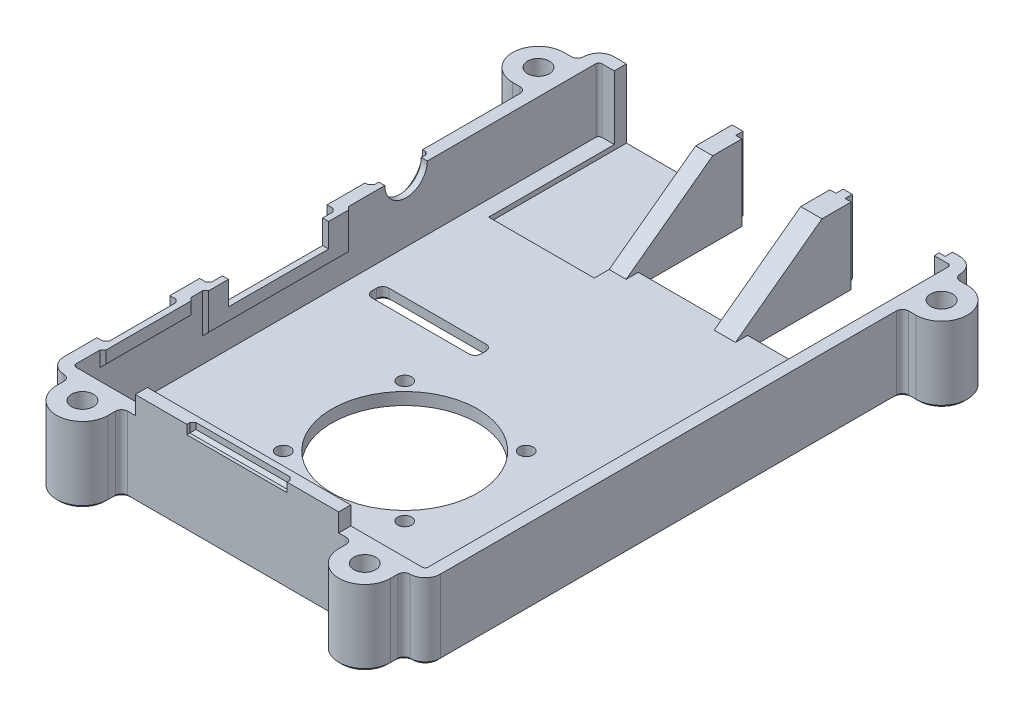
SolidWorks part; units mm, degrees
ref_plane "Front Plane" through (0, 0, 0) normal (0, 0, 1) x (1, 0, 0)
ref_plane "Top Plane" through (0, 0, 0) normal (0, 1, 0) x (1, 0, 0)
ref_plane "Right Plane" through (0, 0, 0) normal (1, 0, 0) x (0, 0, -1)
sketch "Sketch2" plane through (0, 0, 0) normal (0, 1, 0) x (1, 0, 0)
  line L1 (2.5, 0) -> (59.5, 0)
  line L2 (0, 2.5) -> (0, 88.1)
  line L3 (2.5, 90.6) -> (59.5, 90.6)
  line L4 (62, 2.5) -> (62, 88.1)
  arc A0 (0, 2.5) -> (2.5, 0) centre (2.5, 2.5) ccw
  arc A1 (59.5, 0) -> (62, 2.5) centre (59.5, 2.5) ccw
  arc A2 (62, 88.1) -> (59.5, 90.6) centre (59.5, 88.1) ccw
  arc A3 (2.5, 90.6) -> (0, 88.1) centre (2.5, 88.1) ccw
  point P7 (0, 0)
  point P10 (62, 0)
  point P13 (62, 90.6)
  point P16 (0, 90.6)
  dimension "D3" = 2.5
  dimension "D1" = 62
  dimension "D2" = 90.6
extrude "Base" add sketch "Sketch2" along normal blind 12.5
shell "Shell" thickness 2 removed face at (31, 12.5, -45.3)
sketch "Sketch14" plane through (0, 0, 0) normal (0, -1, 0) x (1, 0, 0)
  line L0 (31, 0) -> (31, -90.6) construction
  line L2 (59.5, -90.6) -> (2.5, -90.6) construction
  line L3 (-2.2, -78.6) -> (0, -78.6)
  line L4 (0, -88.1) -> (0, -2.5) construction
  line L5 (0, -78.6) -> (0, -87.1)
  line L6 (0, -87.1) -> (-2.2, -87.1)
  line L7 (3.5, 2.2) -> (3.5, 0)
  line L8 (2.5, 0) -> (59.5, 0) construction
  line L9 (3.5, 0) -> (12, 0)
  line L10 (12, 0) -> (12, 2.2)
  line L11 (64.2, -78.6) -> (62, -78.6)
  line L12 (62, -87.1) -> (64.2, -87.1)
  line L13 (62, -78.6) -> (62, -87.1)
  line L14 (50, 0) -> (50, 2.2)
  line L15 (58.5, 0) -> (50, 0)
  line L16 (58.5, 2.2) -> (58.5, 0)
  line L17 (2.5, 0) -> (59.5, 0) construction
  arc A0 (-2.2, -78.6) -> (-2.2, -87.1) centre (-2.2, -82.85) ccw
  arc A1 (3.5, 2.2) -> (12, 2.2) centre (7.75, 2.2) cw
  arc A2 (64.2, -78.6) -> (64.2, -87.1) centre (64.2, -82.85) cw
  arc A3 (58.5, 2.2) -> (50, 2.2) centre (54.25, 2.2) ccw
  dimension "D1" = 2.2
  dimension "D2" = 8.5
  dimension "D3" = 3.5
  dimension "D4" = 3.5
extrude "Clamps" add sketch "Sketch14" against normal up to surface (12.5 mm away) up to face at (31, 12.5, -45.3)
fillet "Clamp Fillets" radius 1 8 edges at (50, 6.25, 0) (58.5, 6.25, 0) (12, 6.25, 0) (3.5, 6.25, 0) (0, 6.25, -87.1) (0, 6.25, -78.6) (62, 6.25, -78.6) (62, 6.25, -87.1)
sketch "Sketch20" plane through (0, 0, 0) normal (0, -1, 0) x (1, 0, 0)
  circle A0 centre (7.75, 2.2) radius 1.8
  circle A1 centre (54.25, 2.2) radius 1.8
  circle A2 centre (64.2, -82.85) radius 1.8
  circle A3 centre (-2.2, -82.85) radius 1.8
  arc A4 (12, 2.2) -> (3.5, 2.2) centre (7.75, 2.2) ccw construction
  arc A5 (58.5, 2.2) -> (50, 2.2) centre (54.25, 2.2) ccw construction
  arc A6 (-2.2, -78.6) -> (-2.2, -87.1) centre (-2.2, -82.85) ccw construction
  arc A7 (64.2, -87.1) -> (64.2, -78.6) centre (64.2, -82.85) ccw construction
  dimension "D1" = 3.6
extrude "Clamp Holes" cut sketch "Sketch20" against normal through all
sketch "Sketch21" plane through (0, 0, 0) normal (0, -1, 0) x (1, 0, 0)
  circle A0 centre (7.75, 2.2) radius 2.9
  circle A1 centre (54.25, 2.2) radius 2.9
  circle A2 centre (64.2, -82.85) radius 2.9
  circle A3 centre (-2.2, -82.85) radius 2.9
  circle A4 centre (-2.2, -82.85) radius 1.8 construction
  circle A5 centre (7.75, 2.2) radius 1.8 construction
  circle A6 centre (54.25, 2.2) radius 1.8 construction
  circle A7 centre (64.2, -82.85) radius 1.8 construction
  dimension "D1" = 5.8
extrude "Clamp Countersinks" cut sketch "Sketch21" against normal blind 3.4
chamfer "Clamp Countersink Chamfers" distance 0.3 angle 45 4 edges at (-2.2, 0, -85.75) (64.2, 0, -85.75) (54.25, 0, -0.7) (7.75, 0, -0.7)
sketch "Sketch22" plane through (0, 12.5, 0) normal (0, 1, 0) x (1, 0, 0)
  line L0 (31, 2) -> (31, 0) construction
  line L1 (2.5, 2) -> (59.5, 2) construction
  line L2 (13, 0) -> (49, 0) construction
  line L4 (14.25, 2) -> (47.75, 2)
  line L5 (14.25, 2) -> (14.25, 0)
  line L6 (14.25, 0) -> (47.75, 0)
  line L7 (47.75, 2) -> (47.75, 0)
  dimension "D1" = 16.75
  dimension "D2" = 33.5
extrude "SD Fill" add sketch "Sketch22" along normal blind 3
sketch "Sketch23" plane through (0, 0, 0) normal (0, 0, 1) x (1, 0, 0)
  line L0 (31, 15.5) -> (31, 0) construction
  line L1 (14.25, 15.5) -> (47.75, 15.5) construction
  line L2 (13, 0) -> (49, 0) construction
  line L4 (22.75, 15.5) -> (39.25, 15.5)
  line L5 (22.75, 15.5) -> (22.75, 14)
  line L6 (22.75, 14) -> (39.25, 14)
  line L7 (39.25, 15.5) -> (39.25, 14)
  dimension "D1" = 8.25
  dimension "D2" = 16.5
  dimension "D3" = 1.5
extrude "SD Approach" cut sketch "Sketch23" against normal blind 1
chamfer "SD Approach Chamfer" distance 0.5 angle 45 3 edges at (39.25, 14.75, -1) (31, 14, -1) (22.75, 14.75, -1)
sketch "Sketch24" plane through (0, 0, -90.6) normal (0, 0, -1) x (-1, 0, 0)
  line L0 (-59.5, 12.5) -> (-2.5, 12.5) construction
  line L1 (-57.25, 12.5) -> (-42.75, 12.5)
  line L2 (-57.25, 12.5) -> (-57.25, 0)
  line L3 (-57.25, 0) -> (-42.75, 0)
  line L4 (-42.75, 12.5) -> (-42.75, 0)
  line L5 (-59.5, 0) -> (-2.5, 0) construction
  line L6 (0, 12.5) -> (0, 0) construction
  line L7 (-39.25, 12.5) -> (-24.75, 12.5)
  line L8 (-39.25, 12.5) -> (-39.25, 0)
  line L9 (-39.25, 0) -> (-24.75, 0)
  line L10 (-24.75, 12.5) -> (-24.75, 0)
  dimension "D1" = 14.5
  dimension "D2" = 24.75
  dimension "D3" = 42.75
extrude "USB Cutout" cut sketch "Sketch24" against normal blind 18.25
sketch "Sketch25" plane through (0, 0, -90.6) normal (0, 0, -1) x (-1, 0, 0)
  line L0 (-42.75, 12.5) -> (-39.25, 12.5) construction
  line L1 (-41.75, 12.5) -> (-58.25, 12.5)
  line L2 (-41.75, 12.5) -> (-41.75, 0)
  line L3 (-41.75, 0) -> (-58.25, 0)
  line L4 (-58.25, 12.5) -> (-58.25, 0)
  line L5 (-59.5, 0) -> (-57.25, 0) construction
  line L6 (-24.75, 12.5) -> (-2.5, 12.5) construction
  line L7 (-23.75, 12.5) -> (-40.25, 12.5)
  line L8 (-23.75, 12.5) -> (-23.75, 0)
  line L9 (-23.75, 0) -> (-40.25, 0)
  line L10 (-40.25, 12.5) -> (-40.25, 0)
  line L11 (-42.75, 0) -> (-39.25, 0) construction
  line L12 (-57.25, 12.5) -> (-57.25, 0) construction
  line L13 (-42.75, 0) -> (-42.75, 12.5) construction
  line L14 (-39.25, 12.5) -> (-39.25, 0) construction
  line L15 (-24.75, 0) -> (-24.75, 12.5) construction
  point P18 (-57.25, 6.25)
  dimension "D1" = 1
  dimension "D2" = 1
  dimension "D3" = 1
  dimension "D4" = 1
extrude "USB Approach" cut sketch "Sketch25" against normal blind 1.2
sketch "Sketch26" plane through (42.75, 0, 0) normal (1, 0, 0) x (0, 0, -1)
  line L0 (88.6, 2) -> (88.6, 12.5)
  line L1 (88.6, 12.5) -> (84.6, 12.5)
  line L2 (88.6, 2) -> (70.35, 2)
  line L3 (70.35, 2) -> (84.6, 12.5)
  line L4 (90.6, 0) -> (90.6, 12.5) construction
  line L5 (72.35, 0) -> (72.35, 2) construction
  dimension "D1" = 6
  dimension "D2" = 2
extrude "USB Inner Support" add sketch "Sketch26" against normal up to surface (3.5 mm away) up to face at (39.25, 4.8333, -83.45)
sketch "Sketch27" plane through (24.75, 0, 0) normal (1, 0, 0) x (0, 0, -1)
  line L0 (88.6, 2) -> (88.6, 12.5)
  line L1 (88.6, 12.5) -> (84.6, 12.5)
  line L2 (88.6, 2) -> (70.35, 2)
  line L3 (70.35, 2) -> (84.6, 12.5)
  line L4 (90.6, 0) -> (90.6, 12.5) construction
  line L5 (72.35, 0) -> (72.35, 2) construction
  dimension "D1" = 6
  dimension "D2" = 2
extrude "USB Outer Support" add sketch "Sketch27" against normal blind 2.8
sketch "Sketch28" plane through (0, 0, -90.6) normal (0, 0, -1) x (-1, 0, 0)
  line L0 (-23.75, 12.5) -> (-2.5, 12.5) construction
  line L1 (-21.95, 12.5) -> (-4.55, 12.5)
  line L2 (-21.95, 12.5) -> (-21.95, 1.2)
  line L3 (-21.95, 1.2) -> (-4.55, 1.2)
  line L4 (-4.55, 12.5) -> (-4.55, 1.2)
  line L5 (0, 12.5) -> (0, 0) construction
  dimension "D1" = 17.4
  dimension "D2" = 4.55
  dimension "D3" = 11.3
extrude "RJ45 Cutout" cut sketch "Sketch28" against normal blind 22.7
sketch "Sketch29" plane through (2, 0, 0) normal (1, 0, 0) x (0, 0, -1)
  line L0 (88.1, 12.5) -> (2.5, 12.5) construction
  line L1 (6.45, 12.5) -> (21.45, 12.5)
  line L2 (6.45, 12.5) -> (6.45, 10)
  line L3 (6.45, 10) -> (21.45, 10)
  line L4 (21.45, 12.5) -> (21.45, 10)
  line L5 (0, 12.5) -> (0, 0) construction
  line L6 (23.35, 12.5) -> (47.35, 12.5)
  line L7 (23.35, 12.5) -> (23.35, 6.07)
  line L8 (23.35, 6.07) -> (47.35, 6.07)
  line L9 (47.35, 12.5) -> (47.35, 6.07)
  dimension "D1" = 24
  dimension "D2" = 15
  dimension "D3" = 6.45
  dimension "D4" = 23.35
  dimension "D5" = 2.5
  dimension "D6" = 6.43
extrude "HDMI Support" add sketch "Sketch29" along normal blind 0.5
chamfer "HDMI Support Chamfer" distance 0.5 angle 45 6 edges at (2.5, 9.285, -47.35) (2.5, 6.07, -35.35) (2.5, 9.285, -23.35) (2.5, 11.25, -21.45) (2.5, 10, -13.95) (2.5, 11.25, -6.45)
sketch "Sketch30" plane through (0, 0, 0) normal (-1, 0, 0) x (0, 0, 1)
  line L0 (-77.6, 12.5) -> (-2.5, 12.5) construction
  line L1 (-24.85, 12.5) -> (-45.85, 12.5)
  line L2 (-24.85, 12.5) -> (-24.85, 6.57)
  line L3 (-24.85, 6.57) -> (-45.85, 6.57)
  line L4 (-45.85, 12.5) -> (-45.85, 6.57)
  line L5 (0, 12.5) -> (0, 0) construction
  line L6 (-19.95, 12.5) -> (-7.95, 12.5)
  line L7 (-19.95, 12.5) -> (-19.95, 10.5)
  line L8 (-19.95, 10.5) -> (-7.95, 10.5)
  line L9 (-7.95, 12.5) -> (-7.95, 10.5)
  dimension "D1" = 12
  dimension "D2" = 21
  dimension "D3" = 7.95
  dimension "D4" = 24.85
  dimension "D5" = 5.93
  dimension "D6" = 2
extrude "HDMI Approach" cut sketch "Sketch30" against normal blind 1.5
sketch "Sketch31" plane through (1.5, 0, 0) normal (-1, 0, 0) x (0, 0, 1)
  line L0 (-24.85, 12.5) -> (-45.85, 12.5) construction
  line L1 (-43.6, 12.5) -> (-27.1, 12.5)
  line L2 (-43.6, 12.5) -> (-43.6, 8.57)
  line L3 (-43.6, 8.57) -> (-27.1, 8.57)
  line L4 (-27.1, 12.5) -> (-27.1, 8.57)
  line L5 (-45.85, 12.5) -> (-45.85, 6.57) construction
  line L6 (-24.85, 6.57) -> (-24.85, 12.5) construction
  line L7 (-45.85, 6.57) -> (-24.85, 6.57) construction
  dimension "D1" = 2.25
  dimension "D2" = 2.25
  dimension "D3" = 2
extrude "HDMI Cutout" cut sketch "Sketch31" against normal blind 1
chamfer "HDMI Approach Chamfer" distance 0.5 angle 45 6 edges at (1.5, 11.5, -7.95) (1.5, 10.5, -13.95) (1.5, 11.5, -19.95) (1.5, 9.535, -24.85) (1.5, 6.57, -35.35) (1.5, 9.535, -45.85)
sketch "Sketch32" plane through (0, 0, 0) normal (-1, 0, 0) x (0, 0, 1)
  line L0 (-77.6, 12.5) -> (-45.85, 12.5) construction
  line L1 (0, 12.5) -> (0, 0) construction
  circle A0 centre (-56.85, 12.5) radius 3.5
  dimension "D1" = 7
  dimension "D2" = 56.85
extrude "Audio Cutout" cut sketch "Sketch32" against normal blind 2
sketch "Sketch33" plane through (0, 0, 0) normal (-1, 0, 0) x (0, 0, 1)
  circle A0 centre (-56.85, 12.5) radius 4.75
  arc A1 (-60.35, 12.5) -> (-53.35, 12.5) centre (-56.85, 12.5) ccw construction
  dimension "D1" = 9.5
extrude "Audio Approach" cut sketch "Sketch33" against normal blind 1
chamfer "Audio Approach Chamfer" distance 0.5 angle 45 1 edges at (1, 7.75, -56.85)
sketch "Sketch34" plane through (0, 0, 0) normal (0, -1, 0) x (1, 0, 0)
  line L0 (62, -2.5) -> (62, -77.6) construction
  line L1 (52.5, -9.4) -> (58.5, -9.4)
  line L2 (52.5, -9.4) -> (52.5, -62.1)
  line L3 (52.5, -62.1) -> (58.5, -62.1)
  line L4 (58.5, -9.4) -> (58.5, -62.1)
  line L5 (13, 0) -> (49, 0) construction
  point P6 (55.5, -9.4)
  dimension "D1" = 6
  dimension "D2" = 52.7
  dimension "D3" = 3.5
  dimension "D4" = 9.4
extrude "Header Cutout" cut sketch "Sketch34" against normal blind 2
sketch "Sketch35" plane through (0, 0, 0) normal (0, -1, 0) x (1, 0, 0)
  line L0 (55.5, -9.4) -> (55.5, -62.1) construction
  line L1 (58.5, -9.4) -> (52.5, -9.4) construction
  line L2 (52.5, -62.1) -> (58.5, -62.1) construction
  line L3 (52.5, -35.75) -> (58.5, -35.75) construction
  line L4 (52.5, -9.4) -> (52.5, -62.1) construction
  line L5 (58.5, -62.1) -> (58.5, -9.4) construction
  line L6 (56, -9.4) -> (55, -9.4)
  line L7 (55, -9.4) -> (55, -10.4)
  line L8 (55, -10.4) -> (53.5, -10.4)
  line L9 (53.5, -10.4) -> (53.5, -15.3625)
  line L10 (53.5, -15.3625) -> (52.5, -15.3625)
  line L11 (52.5, -15.3625) -> (52.5, -16.3625)
  line L12 (52.5, -16.3625) -> (53.5, -16.3625)
  line L13 (53.5, -16.3625) -> (53.5, -28.2875)
  line L14 (53.5, -28.2875) -> (52.5, -28.2875)
  line L15 (52.5, -28.2875) -> (52.5, -29.2875)
  line L16 (52.5, -29.2875) -> (53.5, -29.2875)
  line L17 (53.5, -29.2875) -> (53.5, -34.25)
  line L18 (53.5, -34.25) -> (55, -34.25)
  line L19 (55, -34.25) -> (55, -35.25)
  line L20 (55, -35.25) -> (52.5, -35.25)
  line L21 (52.5, -35.25) -> (52.5, -36.25)
  line L22 (56, -62.1) -> (55, -62.1)
  line L23 (55, -36.25) -> (52.5, -36.25)
  line L24 (55, -37.25) -> (55, -36.25)
  line L25 (53.5, -37.25) -> (55, -37.25)
  line L26 (53.5, -42.2125) -> (53.5, -37.25)
  line L27 (52.5, -42.2125) -> (53.5, -42.2125)
  line L28 (52.5, -43.2125) -> (52.5, -42.2125)
  line L29 (53.5, -43.2125) -> (52.5, -43.2125)
  line L30 (53.5, -55.1375) -> (53.5, -43.2125)
  line L31 (52.5, -55.1375) -> (53.5, -55.1375)
  line L32 (52.5, -56.1375) -> (52.5, -55.1375)
  line L33 (53.5, -56.1375) -> (52.5, -56.1375)
  line L34 (53.5, -61.1) -> (53.5, -56.1375)
  line L35 (55, -61.1) -> (53.5, -61.1)
  line L36 (55, -62.1) -> (55, -61.1)
  line L37 (56, -62.1) -> (56, -61.1)
  line L38 (56, -61.1) -> (57.5, -61.1)
  line L39 (57.5, -61.1) -> (57.5, -56.1375)
  line L40 (57.5, -56.1375) -> (58.5, -56.1375)
  line L41 (58.5, -56.1375) -> (58.5, -55.1375)
  line L42 (58.5, -55.1375) -> (57.5, -55.1375)
  line L43 (57.5, -55.1375) -> (57.5, -43.2125)
  line L44 (57.5, -43.2125) -> (58.5, -43.2125)
  line L45 (58.5, -43.2125) -> (58.5, -42.2125)
  line L46 (58.5, -42.2125) -> (57.5, -42.2125)
  line L47 (57.5, -42.2125) -> (57.5, -37.25)
  line L48 (57.5, -37.25) -> (56, -37.25)
  line L49 (56, -37.25) -> (56, -36.25)
  line L50 (56, -36.25) -> (58.5, -36.25)
  line L51 (58.5, -35.25) -> (58.5, -36.25)
  line L52 (56, -35.25) -> (58.5, -35.25)
  line L53 (56, -34.25) -> (56, -35.25)
  line L54 (57.5, -34.25) -> (56, -34.25)
  line L55 (57.5, -29.2875) -> (57.5, -34.25)
  line L56 (58.5, -29.2875) -> (57.5, -29.2875)
  line L57 (58.5, -28.2875) -> (58.5, -29.2875)
  line L58 (57.5, -28.2875) -> (58.5, -28.2875)
  line L59 (57.5, -16.3625) -> (57.5, -28.2875)
  line L60 (58.5, -16.3625) -> (57.5, -16.3625)
  line L61 (58.5, -15.3625) -> (58.5, -16.3625)
  line L62 (57.5, -15.3625) -> (58.5, -15.3625)
  line L63 (57.5, -10.4) -> (57.5, -15.3625)
  line L64 (56, -10.4) -> (57.5, -10.4)
  line L65 (56, -9.4) -> (56, -10.4)
  dimension "D1" = 0.5
  dimension "D2" = 1
  dimension "D3" = 1.5
  dimension "D4" = 11.925
extrude "Header Cover" add sketch "Sketch35" against normal blind 1
chamfer "Shell Chamfer" distance 0.5 angle 45 46 edges at (53.75, 0, -62.1) (52.5, 0, -59.1188) (52.5, 0, -49.175) (52.5, 0, -39.2312) (52.5, 0, -32.2687) (52.5, 0, -22.325) (52.5, 0, -12.3812) (53.75, 0, -9.4) (57.25, 0, -9.4) (58.5, 0, -12.3812) (58.5, 0, -22.325) (58.5, 0, -32.2687) (58.5, 0, -39.2312) (58.5, 0, -49.175) (58.5, 0, -59.1187) (57.25, 0, -62.1) (41, 0, -90.6) (58.875, 0, -90.6) (61.2678, 0, -89.8678) (62.2929, 0, -87.3929) (63.6, 0, -87.1) (68.45, 0, -82.85) (63.6, 0, -78.6) (62.2929, 0, -78.3071) (62, 0, -40.05) (13.125, 0, -90.6) (0.7322, 0, -89.8678) (-0.2929, 0, -87.3929) (-1.6, 0, -87.1) (-6.45, 0, -82.85) (-1.6, 0, -78.6) (0, 0, -40.05) (61.2678, 0, -0.7322) (58.7929, 0, 0.2929) (58.5, 0, 1.6) (54.25, 0, 6.45) (50, 0, 1.6) (49.7071, 0, 0.2929) (0.7322, 0, -0.7322) (3.5, 0, 1.6) (7.75, 0, 6.45) (12, 0, 1.6) (12.2929, 0, 0.2929) (31, 0, 0) (-0.2929, 0, -78.3071) (3.2071, 0, 0.2929)
sketch "Sketch38" plane through (0, 0, 0) normal (0, -1, 0) x (1, 0, 0)
  line L0 (31, 0) -> (31, -72.35) construction
  line L1 (13, 0) -> (49, 0) construction
  line L2 (39.25, -72.35) -> (24.75, -72.35) construction
  line L3 (31, -27.63) -> (41, -17.63) construction
  line L4 (31, -27.63) -> (41, -37.63) construction
  circle A0 centre (31, -27.63) radius 12
  circle A1 centre (31, -27.63) radius 14.1421 construction
  circle A2 centre (41, -17.63) radius 1.15
  circle A3 centre (41, -37.63) radius 1.15
  circle A4 centre (21, -17.63) radius 1.15
  circle A5 centre (21, -37.63) radius 1.15
  dimension "D1" = 24
  dimension "D2" = 28.2842
  dimension "D3" = 27.63
  dimension "D6" = 2.3
  dimension "D4" = 45
  dimension "D5" = 45
sketch "Sketch36" plane through (0, 0, 0) normal (0, -1, 0) x (1, 0, 0)
  line L0 (13, 0) -> (49, 0) construction
  line L1 (23.1, -5.7) -> (39.1, -5.7)
  line L2 (22.1, -6.7) -> (22.1, -7.5)
  line L3 (23.1, -8.5) -> (39.1, -8.5)
  line L4 (40.1, -6.7) -> (40.1, -7.5)
  line L5 (0, -77.6) -> (0, -2.5) construction
  line L7 (6.45, -46.76) -> (22.45, -46.76)
  line L8 (5.45, -47.76) -> (5.45, -48.56)
  line L9 (6.45, -49.56) -> (22.45, -49.56)
  line L10 (23.45, -47.76) -> (23.45, -48.56)
  arc A0 (22.1, -7.5) -> (23.1, -8.5) centre (23.1, -7.5) ccw
  arc A1 (39.1, -8.5) -> (40.1, -7.5) centre (39.1, -7.5) ccw
  arc A2 (40.1, -6.7) -> (39.1, -5.7) centre (39.1, -6.7) ccw
  arc A3 (23.1, -5.7) -> (22.1, -6.7) centre (23.1, -6.7) ccw
  arc A4 (5.45, -48.56) -> (6.45, -49.56) centre (6.45, -48.56) ccw
  arc A5 (23.45, -48.56) -> (22.45, -49.56) centre (22.45, -48.56) cw
  arc A6 (23.45, -47.76) -> (22.45, -46.76) centre (22.45, -47.76) ccw
  arc A7 (6.45, -46.76) -> (5.45, -47.76) centre (6.45, -47.76) ccw
  point P14 (40.1, -5.7)
  point P17 (22.1, -5.7)
  point P25 (5.45, -49.56)
  point P28 (23.45, -49.56)
  point P31 (23.45, -46.76)
  dimension "D5" = 46.76
  dimension "D8" = 1
  dimension "D1" = 5.7
  dimension "D2" = 22.1
  dimension "D3" = 2.8
  dimension "D4" = 18
  dimension "D6" = 18
  dimension "D7" = 2.8
  dimension "D9" = 5.45
extrude "Ribbon Slots" cut sketch "Sketch36" against normal blind 2
chamfer "Ribbon Slot Chamfers" distance 0.5 angle 45 16 edges at (14.45, 0, -49.56) (23.1571, 0, -49.2671) (23.45, 0, -48.16) (23.1571, 0, -47.0529) (14.45, 0, -46.76) (5.7429, 0, -49.2671) (5.45, 0, -48.16) (5.7429, 0, -47.0529) (31.1, 0, -8.5) (39.8071, 0, -8.2071) (40.1, 0, -7.1) (39.8071, 0, -5.9929) (31.1, 0, -5.7) (22.3929, 0, -5.9929) (22.1, 0, -7.1) (22.3929, 0, -8.2071)
extrude "Fan Mount" cut sketch "Sketch38" against normal blind 2
